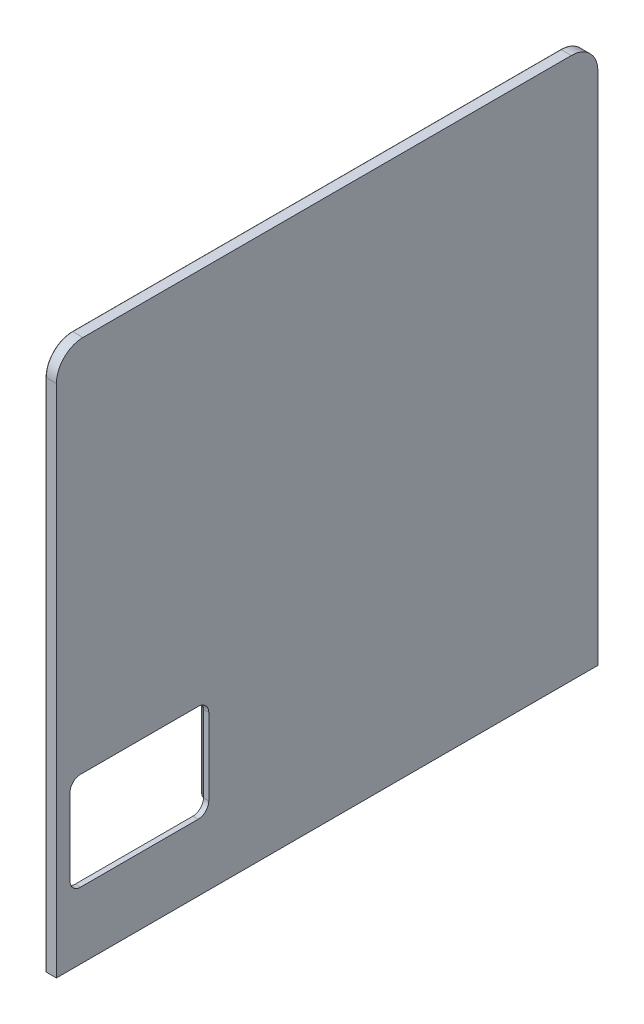
SolidWorks part; units mm, degrees
ref_plane "Front Plane" through (0, 0, 0) normal (0, 0, 1) x (1, 0, 0)
ref_plane "Top Plane" through (0, 0, 0) normal (0, 1, 0) x (1, 0, 0)
ref_plane "Right Plane" through (0, 0, 0) normal (1, 0, 0) x (0, 0, -1)
sketch "Sketch1" plane through (0, 0, 0) normal (1, 0, 0) x (0, 0, -1)
  line L1 (-102, -102) -> (102, -102)
  line L2 (-102, -102) -> (-102, 92)
  line L3 (-92, 102) -> (92, 102)
  line L4 (102, -102) -> (102, 92)
  line L5 (-102, -102) -> (102, 102) construction
  line L6 (-102, 102) -> (102, -102) construction
  arc A2 (-102, 92) -> (-92, 102) centre (-92, 92) cw
  arc A3 (92, 102) -> (102, 92) centre (92, 92) cw
  point P0 (0, 0)
  dimension "D1" = 204
  dimension "D2" = 204
extrude "Boss-Extrude1" add sketch "Sketch1" along normal blind 4
sketch "Sketch2" plane through (4, 0, 0) normal (1, 0, 0) x (0, 0, -1)
  line L1 (92, 102) -> (-92, 102) construction
  line L37 (102, -102) -> (102, 92) construction
  line L40 (-100.1, 90.3) -> (-100.1, -70.3)
  line L41 (-90.3, 100.1) -> (90.3, 100.1)
  line L42 (100.1, 90.3) -> (100.1, -90.3)
  line L43 (90.3, -100.1) -> (-100.1, -100.1)
  line L44 (-100.1, -100.1) -> (-100.1, -98.7)
  line L45 (-97.3, -95.9) -> (85.7, -95.9)
  line L46 (85.7, 95.9) -> (-85.7, 95.9)
  line L47 (-95.9, 85.7) -> (-95.9, -35.9)
  line L48 (-90.9, -75.9) -> (-48.6, -75.9)
  line L49 (75.9, -65.7) -> (75.9, 78)
  line L50 (-90.3, -80.1) -> (70.3, -80.1)
  line L51 (95.9, -85.7) -> (95.9, 85.7)
  line L52 (80.1, 78) -> (80.1, -70.3)
  line L53 (-92.9, -41.1) -> (-49.6, -41.1)
  line L54 (-45.6, -45.1) -> (-45.6, -61.9)
  line L55 (-43.4, -72.9) -> (-43.4, -42.9)
  line L56 (-47.4, -38.9) -> (-92.9, -38.9)
  line L57 (-95.9, -44.1) -> (-95.9, -61.9)
  line L58 (-40.4, -75.9) -> (65.7, -75.9)
  line L59 (-95.9, -61.9) -> (-94.9, -61.9)
  line L60 (-94.9, -61.9) -> (-94.9, -63.6)
  line L61 (-94.9, -63.6) -> (-95.9, -63.6)
  line L62 (-95.9, -65.3) -> (-94.9, -65.3)
  line L63 (-94.9, -65.3) -> (-94.9, -67)
  line L64 (-94.9, -67) -> (-95.9, -67)
  line L65 (-95.9, -63.6) -> (-95.9, -65.3)
  line L66 (-95.9, -67) -> (-95.9, -70.9)
  line L67 (-45.6, -61.9) -> (-46.4, -61.9)
  line L68 (-46.4, -61.9) -> (-46.4, -63.5)
  line L69 (-46.4, -63.5) -> (-45.6, -63.5)
  line L70 (-45.6, -67) -> (-46.4, -67)
  line L71 (-46.4, -67) -> (-46.4, -65.4)
  line L72 (-46.4, -65.4) -> (-45.6, -65.4)
  line L73 (-45.6, -63.5) -> (-45.6, -65.4)
  line L74 (-45.6, -67) -> (-45.6, -72.9)
  arc A32 (-95.9, -70.9) -> (-90.9, -75.9) centre (-90.9, -70.9) ccw
  arc A33 (65.7, -75.9) -> (75.9, -65.7) centre (65.7, -65.7) ccw
  arc A34 (-85.7, 95.9) -> (-95.9, 85.7) centre (-85.7, 85.7) ccw
  arc A35 (-100.1, 90.3) -> (-90.3, 100.1) centre (-90.3, 90.3) cw
  arc A36 (100.1, -90.3) -> (90.3, -100.1) centre (90.3, -90.3) cw
  arc A37 (85.7, -95.9) -> (95.9, -85.7) centre (85.7, -85.7) ccw
  arc A38 (80.1, -70.3) -> (70.3, -80.1) centre (70.3, -70.3) cw
  arc A39 (85.7, 95.9) -> (95.9, 85.7) centre (85.7, 85.7) cw
  arc A40 (90.3, 100.1) -> (100.1, 90.3) centre (90.3, 90.3) cw
  arc A41 (75.9, 78) -> (80.1, 78) centre (78, 78) cw
  arc A42 (-100.1, -98.7) -> (-97.3, -95.9) centre (-97.3, -98.7) cw
  arc A43 (-100.1, -70.3) -> (-90.3, -80.1) centre (-90.3, -70.3) ccw
  arc A44 (-43.4, -42.9) -> (-47.4, -38.9) centre (-47.4, -42.9) ccw
  arc A45 (-49.6, -41.1) -> (-45.6, -45.1) centre (-49.6, -45.1) cw
  arc A46 (-40.4, -75.9) -> (-43.4, -72.9) centre (-40.4, -72.9) cw
  arc A47 (-92.9, -38.9) -> (-95.9, -35.9) centre (-92.9, -35.9) cw
  arc A48 (-45.6, -72.9) -> (-48.6, -75.9) centre (-48.6, -72.9) cw
  arc A49 (-92.9, -41.1) -> (-95.9, -44.1) centre (-92.9, -44.1) ccw
  point P63 (-95.4, -65.3)
  dimension "D19" = 2.1
  dimension "D26" = 4
  dimension "D27" = 3
  dimension "D5" = 4.2
  dimension "D9" = 9.8
  dimension "D24" = 2.2
  dimension "D33" = 1.9
  dimension "D35" = 50.3
  dimension "D15" = 10.2
  dimension "D16" = 9.8
  dimension "D17" = 10.2
  dimension "D18" = 9.8
  dimension "D12" = 4.2
  dimension "D13" = 15.8
  dimension "D6" = 10.2
  dimension "D7" = 10.2
  dimension "D8" = 9.8
  dimension "D21" = 2.8
  dimension "D22" = 9.8
  dimension "D23" = 5
  dimension "D28" = 3
  dimension "D1" = 4.2
  dimension "D2" = 4.2
  dimension "D3" = 4.2
  dimension "D4" = 15.8
  dimension "D10" = 200.2
  dimension "D11" = 200.2
  dimension "D14" = 4.2
  dimension "D20" = 15.8
  dimension "D25" = 2.2
  dimension "D29" = 1.7
  dimension "D30" = 1.7
  dimension "D31" = 1
  dimension "D32" = 20.8
  dimension "D36" = 34.8
  dimension "D37" = 1.9
  dimension "D38" = 1.9
extrude "Cut-Extrude3" cut sketch "Sketch2" along normal blind 2 from surface starting at face at (0, 31.357, 0)
fillet "Fillet1" radius 0.2 59 edges at (0, 99.0711, -99.0711) (0, 102, 0) (0, 99.0711, 99.0711) (0, -5, 102) (0, -102, 0) (0, -5, -102) (0, 0, -100.1) (0, -96.7201, 99.2799) (0, -95.9, 5.8) (0, -92.9125, -92.9125) (0, 0, -95.9) (0, 92.9125, -92.9125) (0, 95.9, 0) (0, 92.9125, 92.9125) (0, 24.9, 95.9) (0, -38.0213, 95.0213) (0, -38.9, 70.15) (0, -40.0716, 44.5716) (0, -57.9, 43.4) (0, -75.0213, 42.5213) (0, -75.9, -12.65) (0, -72.9125, -72.9125) (0, 6.15, -75.9) (0, 80.1, -78) (0, 3.85, -80.1) (0, -77.2296, -77.2296) (0, -80.1, 10) (0, -77.2296, 97.2296) (0, 10, 100.1) (0, 97.2296, 97.2296) (0, 100.1, 0) (0, 97.2296, -97.2296) (0, -97.2296, -97.2296) (0, -100.1, 4.9) (0, -99.4, 100.1) (0, -68.95, 95.9) (0, -74.4355, 94.4355) (0, -75.9, 69.75) (0, -75.0213, 46.4787) (0, -69.95, 45.6) (0, -67, 46) (0, -66.2, 46.4) (0, -65.4, 46) (0, -64.45, 45.6) (0, -63.5, 46) (0, -62.7, 46.4) (0, -61.9, 46) (0, -53.5, 45.6) (0, -42.2716, 46.7716) (0, -41.1, 71.25) (0, -41.9787, 95.0213) (0, -53, 95.9) (0, -61.9, 95.4) (0, -62.75, 94.9) (0, -63.6, 95.4) (0, -64.45, 95.9) (0, -65.3, 95.4) (0, -66.15, 94.9) (0, -67, 95.4)
sketch "Sketch4" plane through (4, 0, 0) normal (1, 0, 0) x (0, 0, -1)
  line L1 (-92.9, -40.1) -> (-48.6, -40.1)
  line L2 (-96.9, -44.1) -> (-96.9, -72.9)
  line L3 (-92.9, -76.9) -> (-48.6, -76.9)
  line L4 (-44.6, -44.1) -> (-44.6, -72.9)
  line L6 (-92.9, -41.1) -> (-49.6, -41.1) construction
  line L7 (-90.9, -75.9) -> (-48.6, -75.9) construction
  line L8 (-45.6, -45.1) -> (-45.6, -61.9) construction
  line L9 (-95.9, -44.1) -> (-95.9, -61.9) construction
  arc A2 (-48.6, -76.9) -> (-44.6, -72.9) centre (-48.6, -72.9) ccw
  arc A3 (-96.9, -72.9) -> (-92.9, -76.9) centre (-92.9, -72.9) ccw
  arc A4 (-48.6, -40.1) -> (-44.6, -44.1) centre (-48.6, -44.1) cw
  arc A5 (-92.9, -40.1) -> (-96.9, -44.1) centre (-92.9, -44.1) ccw
  dimension "D1" = 4
  dimension "D2" = 1
  dimension "D3" = 1
  dimension "D4" = 1
  dimension "D5" = 1
extrude "Cut-Extrude4" cut sketch "Sketch4" against normal up to next
sketch "Sketch5" plane through (0, 0, 0) normal (-1, 0, 0) x (0, 0, 1)
  line L0 (-85.7, 95.9) -> (85.7, 95.9) construction
  line L1 (-58.7, -65.7) -> (-1.1, -65.7)
  line L2 (-65.7, -58.7) -> (-65.7, 78.9)
  line L3 (-58.7, 85.9) -> (-1.1, 85.9)
  line L4 (5.9, -58.7) -> (5.9, 78.9)
  line L5 (-65.7, -65.7) -> (5.9, 85.9) construction
  line L6 (-65.7, 85.9) -> (5.9, -65.7) construction
  line L7 (22.9, -28.7) -> (78.9, -28.7)
  line L8 (15.9, -21.7) -> (15.9, 78.9)
  line L9 (22.9, 85.9) -> (78.9, 85.9)
  line L10 (85.9, -21.7) -> (85.9, 78.9)
  line L11 (15.9, -28.7) -> (85.9, 85.9) construction
  line L12 (15.9, 85.9) -> (85.9, -28.7) construction
  line L13 (47.4, -38.7) -> (92.9, -38.7) construction
  line L14 (95.9, 85.7) -> (95.9, -35.9) construction
  line L15 (-75.7, 78) -> (-75.7, -65.7) construction
  line L16 (-65.7, -75.7) -> (40.4, -75.7) construction
  arc A0 (-1.1, -65.7) -> (5.9, -58.7) centre (-1.1, -58.7) ccw
  arc A1 (-58.7, -65.7) -> (-65.7, -58.7) centre (-58.7, -58.7) cw
  arc A2 (-1.1, 85.9) -> (5.9, 78.9) centre (-1.1, 78.9) cw
  arc A3 (-65.7, 78.9) -> (-58.7, 85.9) centre (-58.7, 78.9) cw
  arc A4 (15.9, 78.9) -> (22.9, 85.9) centre (22.9, 78.9) cw
  arc A5 (22.9, -28.7) -> (15.9, -21.7) centre (22.9, -21.7) cw
  arc A6 (78.9, -28.7) -> (85.9, -21.7) centre (78.9, -21.7) ccw
  arc A7 (78.9, 85.9) -> (85.9, 78.9) centre (78.9, 78.9) cw
  point P0 (-29.9, 10.1)
  point P5 (50.9, 28.6)
  dimension "D9" = 7
  dimension "D1" = 10
  dimension "D2" = 10
  dimension "D3" = 10
  dimension "D4" = 10
  dimension "D5" = 70
  dimension "D6" = 10
  dimension "D7" = 10
  dimension "D8" = 10
extrude "Cut-Extrude5" cut sketch "Sketch5" against normal blind 1
fillet "Fillet2" radius 1 16 edges at (0, 85.9, 50.9) (0, 83.8497, 83.8497) (0, 28.6, 85.9) (0, -26.6497, 83.8497) (0, -28.7, 50.9) (0, -26.6497, 17.9503) (0, 28.6, 15.9) (0, 85.9, -29.9) (0, 83.8497, 3.8497) (0, 10.1, 5.9) (0, -63.6497, 3.8497) (0, -65.7, -29.9) (0, -63.6497, -63.6497) (0, 10.1, -65.7) (0, 83.8497, 17.9503) (0, 83.8497, -63.6497)
